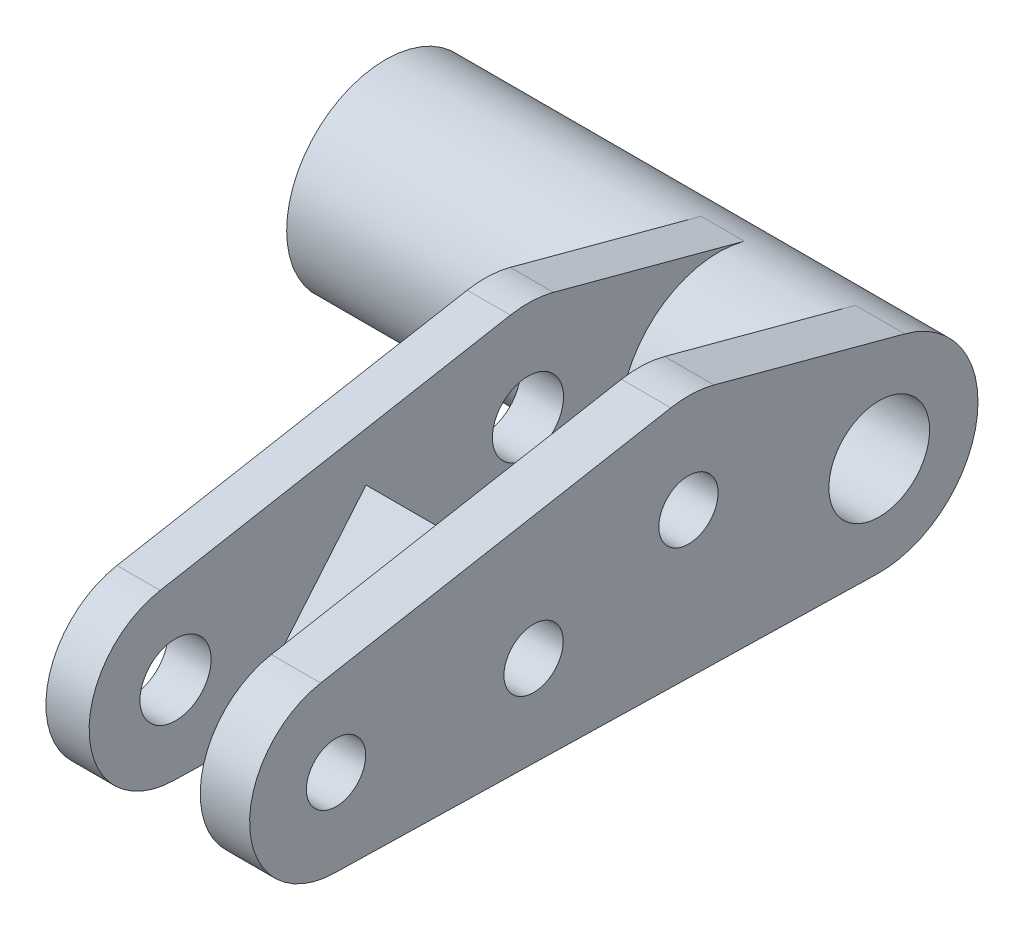
SolidWorks part; units mm, degrees
ref_plane "Front Plane" through (0, 0, 0) normal (0, 0, 1) x (1, 0, 0)
ref_plane "Top Plane" through (0, 0, 0) normal (0, 1, 0) x (1, 0, 0)
ref_plane "Right Plane" through (0, 0, 0) normal (1, 0, 0) x (0, 0, -1)
sketch "Sketch1" plane through (0, 0, 0) normal (1, 0, 0) x (0, 0, -1)
  line L0 (-0.1443, -6.3484) -> (-35.0513, -5.5548)
  line L1 (-35.9129, 5.4677) -> (-13.3962, 9.5358)
  line L2 (-10.6238, 9.4206) -> (1.6435, 6.1336)
  line L3 (-34.925, 0) -> (0, 0) construction
  line L4 (0, 0) -> (-12.2673, 3.287) construction
  arc A0 (-0.1443, -6.3484) -> (1.6435, 6.1336) centre (0, 0) ccw
  arc A1 (-35.0513, -5.5548) -> (-35.9129, 5.4677) centre (-34.925, 0) cw
  arc A2 (-13.3962, 9.5358) -> (-10.6238, 9.4206) centre (-12.2673, 3.287) cw
  dimension "D1" = 6.35
  dimension "D2" = 11.1125
  dimension "D3" = 34.925
  dimension "D4" = 12.7
  dimension "D5" = 15
extrude "Boss-Extrude1" add sketch "Sketch1" against normal blind 13.0969
sketch "Sketch6" plane through (0, 0, 0) normal (1, 0, 0) x (0, 0, -1)
  line L0 (1.6435, 6.1336) -> (-10.6238, 9.4206) construction
  line L1 (-13.3962, 9.5358) -> (-35.9129, 5.4677) construction
  line L2 (1.6435, 6.1336) -> (-10.6238, 9.4206)
  line L3 (-13.3962, 9.5358) -> (-35.9129, 5.4677)
  line L5 (-22.6776, 4.7171) -> (-30.0606, -4.0817)
  line L6 (-35.0513, -5.5548) -> (-0.1443, -6.3484) construction
  line L7 (-35.0513, -5.5548) -> (-31.9779, -5.6247)
  line L8 (-34.925, 0) -> (0, 0) construction
  line L9 (-16.7574, -1.2031) -> (-22.6776, 4.7171)
  arc A0 (-10.6238, 9.4206) -> (-13.3962, 9.5358) centre (-12.2673, 3.287) ccw construction
  arc A1 (-35.9129, 5.4677) -> (-35.0513, -5.5548) centre (-34.925, 0) ccw construction
  arc A2 (-10.6238, 9.4206) -> (-13.3962, 9.5358) centre (-12.2673, 3.287) ccw
  arc A3 (-35.9129, 5.4677) -> (-35.0513, -5.5548) centre (-34.925, 0) ccw
  arc A4 (1.6435, 6.1336) -> (-6.1336, 1.6435) centre (0, 0) ccw
  arc A5 (-6.1336, 1.6435) -> (-16.7574, -1.2031) centre (-12.2673, 3.287) cw
  arc A6 (-30.0606, -4.0817) -> (-31.9779, -5.6247) centre (-34.925, 0) cw
  point P14 (-21.2694, 9.356)
  point P16 (-22.4999, 9.0308)
  point P17 (-22.6018, 7.4787)
  point P18 (-36.5593, 5.3718)
  dimension "D1" = 6.35
  dimension "D2" = 50
  dimension "D3" = 45
extrude "Cut-Extrude4" cut sketch "Sketch6" against normal blind 7.1437 from offset 3.175 offset against normal yes
sketch "Sketch3" plane through (0, 0, 0) normal (1, 0, 0) x (0, 0, -1)
  circle A0 centre (0, 0) radius 3.2385
  circle A1 centre (-34.925, 0) radius 1.905
  circle A2 centre (-12.2673, 3.287) radius 1.905
  circle A3 centre (-22.225, 0) radius 1.905
  circle A4 centre (-22.225, 0) radius 4.445 construction
  circle A5 centre (-34.925, 0) radius 4.445 construction
  point P13 (-26.035, 0)
  point P14 (-26.0634, 0.7101)
  point P15 (-21.2391, 0)
  dimension "D1" = 3.81
  dimension "D2" = 6.477
  dimension "D3" = 8.89
  dimension "D4" = 22.225
extrude "Cut-Extrude2" cut sketch "Sketch3" against normal through all
sketch "Sketch4" plane through (-13.0969, 0, 0) normal (-1, 0, 0) x (0, 0, 1)
  circle A0 centre (0, 0) radius 6.35
  circle A1 centre (0, 0) radius 3.2385
  circle A2 centre (0, 0) radius 3.2385 construction
  arc A3 (-1.6435, 6.1336) -> (0.1443, -6.3484) centre (0, 0) ccw construction
extrude "Boss-Extrude2" add sketch "Sketch4" along normal up to surface (18.6531 mm away)
sketch "Sketch5" plane through (-13.0969, 0, 0) normal (-1, 0, 0) x (0, 0, 1)
  circle A0 centre (12.2673, 3.287) radius 2.286
  circle A1 centre (22.225, 0) radius 2.286
  circle A2 centre (34.925, 0) radius 2.286
  dimension "D1" = 4.572
extrude "Cut-Extrude5" cut sketch "Sketch5" against normal up to surface (2.7781 mm away) up to face at (-10.3187, 3.287, 10.3623)
